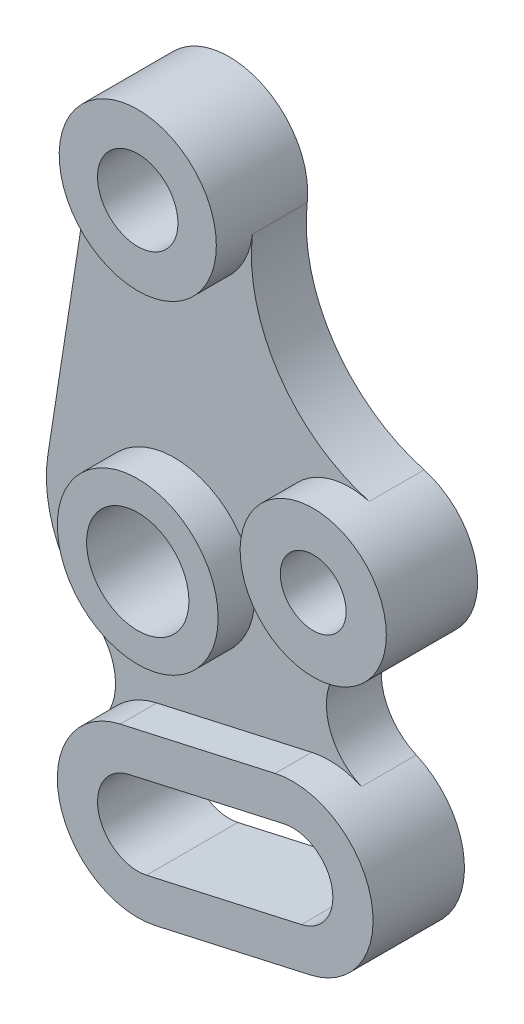
SolidWorks part; units mm, degrees
material "AISI 4130 Steel, normalized at 870C"
ref_plane "Front Plane" through (0, 0, 0) normal (0, 0, 1) x (1, 0, 0)
ref_plane "Top Plane" through (0, 0, 0) normal (0, 1, 0) x (1, 0, 0)
ref_plane "Right Plane" through (0, 0, 0) normal (1, 0, 0) x (0, 0, -1)
sketch "Sketch1" plane through (0, 0, 0) normal (0, 0, 1) x (1, 0, 0)
  line L0 (0, -120) -> (84.759, -101.0119) construction
  line L1 (-9.6187, -77.0642) -> (75.1404, -58.0761)
  line L2 (9.6187, -162.9358) -> (94.3777, -143.9477)
  line L3 (-42.491, 182.5966) -> (-69.1714, 10.7386)
  line L4 (-4.8093, -98.5321) -> (79.9497, -79.544)
  line L5 (4.8093, -141.4679) -> (89.5684, -122.4798)
  line L6 (0, -120) -> (0, 0) construction
  line L7 (0, 0) -> (84.759, -101.0119) construction
  circle A0 centre (0, 0) radius 28
  circle A1 centre (0, 0) radius 44
  circle A2 centre (0, 176) radius 43
  circle A3 centre (0, 176) radius 22
  arc A4 (-9.6187, -77.0642) -> (9.6187, -162.9358) centre (0, -120) ccw
  arc A5 (94.3777, -143.9477) -> (75.1404, -58.0761) centre (84.759, -101.0119) ccw
  circle A6 centre (96, 38) radius 18
  circle A7 centre (96, 38) radius 40
  arc A8 (-69.1714, 10.7386) -> (-44.0402, -54.4101) centre (0, 0) ccw
  arc A9 (-44.0402, -54.4101) -> (-37.1527, -96.4272) centre (-64.1728, -79.2833) cw
  arc A10 (106.6808, -0.5476) -> (102.3975, -60.702) centre (115.2254, -31.3858) ccw
  arc A11 (106.6808, 76.5476) -> (42.7304, 171.192) centre (130.1785, 161.3525) cw
  arc A12 (89.5684, -122.4798) -> (79.9497, -79.544) centre (84.759, -101.0119) ccw
  arc A13 (-4.8093, -98.5321) -> (4.8093, -141.4679) centre (0, -120) ccw
  point P9 (42.3795, -110.506)
  point P19 (0, 0)
  point P36 (0, 0)
  point P38 (0, 0)
  point P39 (0, 0)
  point P40 (-37.9522, -98.2704)
  point P41 (78.0004, -92.9573)
  dimension "D1" = 44
  dimension "D3" = 80
  dimension "D4" = 36
  dimension "D5" = 88
  dimension "D6" = 56
  dimension "D7" = 70
  dimension "D8" = 38
  dimension "D10" = 32
  dimension "D11" = 86
  dimension "D12" = 44
  dimension "D16" = 88
  dimension "D9" = 96
  dimension "D13" = 40
  dimension "D14" = 176
  dimension "D15" = 120
  dimension "D2" = 22
extrude "Boss-Extrude1" add sketch "Sketch1" along normal blind 30 contours A7 A11 A2 L3 A8 A9 A4 L1 A5 A10 A1 region at (-27.2103, -81.3072, 0)
extrude "Boss-Extrude2" add sketch "Sketch1<3>" along normal blind 50 contours A2 A3 | A7 A6 | A1 A0 | L2 A5 L1 A4 A13 L4 A12 L5 region at (33.2051, -69.5531, 0) region at (57.1314, 38, 0) region at (3.2145, 217.6599, 0) region at (-42.7555, 0, 0)
sketch "Sketch1<3>" plane through (0, 0, 0) normal (0, 0, 1) x (1, 0, 0) same geometry as "Sketch1"
